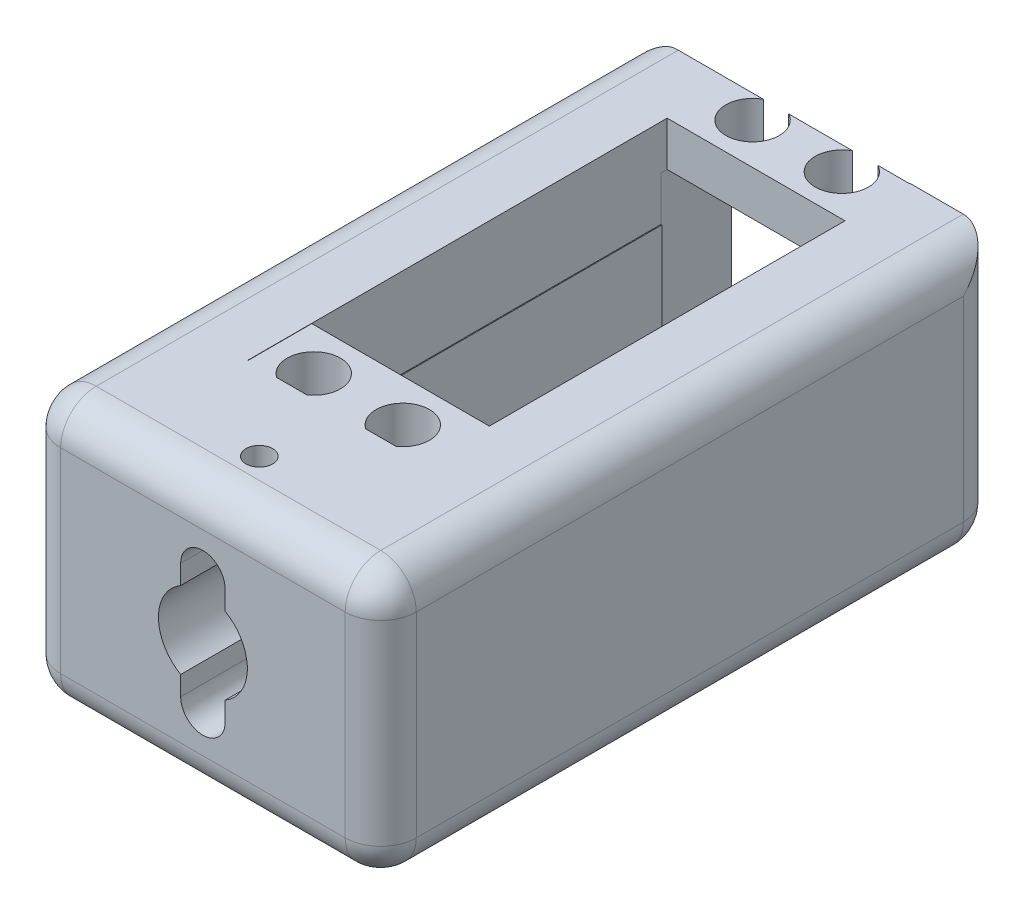
SolidWorks part; units mm, degrees
ref_plane "Front Plane" through (0, 0, 0) normal (0, 0, 1) x (1, 0, 0)
ref_plane "Top Plane" through (0, 0, 0) normal (0, 1, 0) x (1, 0, 0)
ref_plane "Right Plane" through (0, 0, 0) normal (1, 0, 0) x (0, 0, -1)
sketch "Sketch3" plane through (0, 27.7, 0) normal (0, -1, 0) x (1, 0, 0)
  line L0 (10, 7.15) -> (10, -0.3675) construction
  line L1 (-9.9707, 7.2207) -> (10, 7.2207)
  line L2 (-9.9707, 7.2207) -> (-9.9707, 0)
  line L3 (-9.9707, 0) -> (10, 0)
  line L4 (10, 7.2207) -> (10, 0)
  arc A0 (-9.9, 7.25) -> (-10, 7.15) centre (-9.9, 7.15) ccw construction
extrude "Boss-Extrude2" add sketch "Sketch3" along normal blind 10
sketch "Sketch4" plane through (10, 0, 0) normal (1, 0, 0) x (0, 0, -1)
  line L1 (-7.2207, 27.7) -> (47.3058, 27.7)
  line L2 (-7.2207, 27.7) -> (-7.2207, 17.7)
  line L3 (-7.2207, 17.7) -> (47.3058, 17.7)
  line L4 (47.3058, 27.7) -> (47.3058, 17.7)
extrude "Boss-Extrude3" add sketch "Sketch4" along normal blind 10
sketch "Sketch5" plane through (10, 0, 0) normal (-1, 0, 0) x (0, 0, 1)
  line L0 (-40, 11.1) -> (-40, 27.6) construction
  line L1 (-47.25, 27.8) -> (-40, 27.8)
  line L2 (-47.25, 27.8) -> (-47.25, 17.7)
  line L3 (-47.25, 17.7) -> (-40, 17.7)
  line L4 (-40, 27.8) -> (-40, 17.7)
  line L5 (0, 17.7) -> (-47.3058, 17.7) construction
extrude "Boss-Extrude4" add sketch "Sketch5" along normal blind 20
sketch "Sketch6" plane through (-10, 0, 0) normal (-1, 0, 0) x (0, 0, 1)
  line L1 (-47.25, 17.7) -> (7.2207, 17.7)
  line L2 (-47.25, 17.7) -> (-47.25, 27.7)
  line L3 (-47.25, 27.7) -> (7.2207, 27.7)
  line L4 (7.2207, 17.7) -> (7.2207, 27.7)
extrude "Boss-Extrude5" add sketch "Sketch6" along normal blind 10
sketch "Sketch7" plane through (0, 27.8, 0) normal (0, 1, 0) x (1, 0, 0)
  circle A0 centre (-5.0006, 44.6092) radius 3
  circle A1 centre (5.0371, 44.6092) radius 2.9988
extrude "Cut-Extrude1" cut sketch "Sketch7" against normal blind 12
sketch "Sketch8" plane through (0, 27.7, 0) normal (0, 1, 0) x (1, 0, 0)
  circle A0 centre (-5, -4.75) radius 3
  circle A1 centre (5.0146, -4.75) radius 3
extrude "Cut-Extrude2" cut sketch "Sketch8" against normal blind 12
sketch "Sketch9" plane through (0, 17.7, 0) normal (0, -1, 0) x (1, 0, 0)
  line L1 (-20, 7.2207) -> (20, 7.2207)
  line L2 (-20, 7.2207) -> (-20, -47.3058)
  line L3 (-20, -47.3058) -> (20, -47.3058)
  line L4 (20, 7.2207) -> (20, -47.3058)
  line L5 (-9.9, 0) -> (10, 0)
  line L6 (-9.9, 0) -> (-9.9, -40)
  line L7 (-9.9, -40) -> (10, -40)
  line L8 (10, 0) -> (10, -40)
extrude "Boss-Extrude8" add sketch "Sketch9" along normal blind 12
sketch "Sketch10" plane through (0, 0, -47.3058) normal (0, 0, -1) x (-1, 0, 0)
  line L0 (-20, 27.7) -> (-10, 27.7) construction
  line L1 (-10, 27.7) -> (10.06, 27.7)
  line L2 (-10, 27.7) -> (-10, 5.7)
  line L3 (-10, 5.7) -> (10.06, 5.7)
  line L4 (10.06, 27.7) -> (10.06, 5.7)
  line L5 (20, 5.7) -> (-20, 5.7) construction
  line L7 (-10, 27.7) -> (10.06, 27.7)
  line L8 (-10, 27.7) -> (-10, 22.7)
  line L9 (-10, 22.7) -> (10.06, 22.7)
  line L10 (10.06, 27.7) -> (10.06, 22.7)
  line M3 (-10, 17.7) -> (-10, 27.7)
  line M6 (-20, 5.7) -> (20, 5.7)
  line M8 (20, 17.7) -> (-10, 17.7)
  dimension "D1" = 5
extrude "Cut-Extrude6" cut sketch "Sketch10" against normal blind 8 contours L4 L2 M8 M6 | L9 L4 M3 M8 region at (-0.03, 20.2, -47.3058) region at (-0.03, 11.7, -47.3058)
sketch "Sketch11" plane through (0, 0, 7.2207) normal (0, 0, 1) x (1, 0, 0)
  line L1 (-20, 27.7) -> (20, 27.7)
  line L2 (-20, 27.7) -> (-20, 5.7)
  line L3 (-20, 5.7) -> (20, 5.7)
  line L4 (20, 27.7) -> (20, 5.7)
extrude "Boss-Extrude9" add sketch "Sketch11" along normal blind 5
sketch "Sketch12" plane through (10, 0, 0) normal (1, 0, 0) x (0, 0, -1)
  line L1 (40, 27.8) -> (47.25, 27.8)
  line L2 (40, 27.8) -> (40, 27.7)
  line L3 (40, 27.7) -> (47.25, 27.7)
  line L4 (47.25, 27.8) -> (47.25, 27.7)
extrude "Cut-Extrude7" cut sketch "Sketch12" against normal blind 20
sketch "Sketch13" plane through (0, 0, 12.2207) normal (0, 0, 1) x (1, 0, 0)
  line L1 (-10, 27.7) -> (10, 27.7)
  line L2 (-10, 27.7) -> (-10, 5.7)
  line L3 (-10, 5.7) -> (10, 5.7)
  line L4 (10, 27.7) -> (10, 5.7)
  line L5 (-10, 22.7) -> (10, 22.7)
  line M2 (-20, 5.7) -> (20, 5.7)
extrude "Cut-Extrude8" cut sketch "Sketch13" against normal blind 20 contours L5 L2 L4 M2 region at (0, 14.2, 12.2207)
sketch "Sketch16" plane through (0, 5.7, 0) normal (0, -1, 0) x (1, 0, 0)
  line L1 (-20, 12.2207) -> (20, 12.2207)
  line L2 (-20, 12.2207) -> (-20, -47.3058)
  line L3 (-20, -47.3058) -> (20, -47.3058)
  line L4 (20, 12.2207) -> (20, -47.3058)
extrude "Boss-Extrude11" add sketch "Sketch16" along normal blind 8
sketch "Sketch17" plane through (0, 5.7, 0) normal (0, 1, 0) x (1, 0, 0)
  line L0 (10, 0.3675) -> (10, -7.15) construction
  line L1 (-10, 40) -> (10, 40)
  line L2 (-10, 40) -> (-10, 0)
  line L3 (-10, 0) -> (10, 0)
  line L4 (10, 40) -> (10, 0)
  line L5 (10, 0) -> (10, -12.2207) construction
extrude "Cut-Extrude10" cut sketch "Sketch17" against normal blind 5
sketch "Sketch19" plane through (0, 0, 12.2207) normal (0, 0, 1) x (1, 0, 0)
  line L0 (20, -2.3) -> (20, 27.7) construction
  line L1 (-20, 27.7) -> (20, 27.7)
  line L2 (-20, 27.7) -> (-20, -2.3)
  line L3 (-20, -2.3) -> (20, -2.3)
  line L4 (20, 27.7) -> (20, -2.3)
extrude "Boss-Extrude12" add sketch "Sketch19" along normal blind 10
sketch "Sketch20" plane through (0, 0, 22.2207) normal (0, 0, 1) x (1, 0, 0)
  line L0 (0, 6.2) -> (0, 19.2) construction
  line L1 (-2.5, 6.2) -> (-2.5, 8.3699)
  line L2 (2.5, 6.2) -> (2.5, 8.3699)
  line L3 (-20, -2.3) -> (20, -2.3) construction
  line L4 (-2.5, 17.0301) -> (-2.5, 19.2)
  line L5 (2.5, 17.0301) -> (2.5, 19.2)
  arc A0 (-2.5, 6.2) -> (2.5, 6.2) centre (0, 6.2) ccw
  arc A1 (2.5, 19.2) -> (-2.5, 19.2) centre (0, 19.2) ccw
  arc A2 (-2.5, 17.0301) -> (-2.5, 8.3699) centre (0, 12.7) ccw
  arc A3 (2.5, 8.3699) -> (2.5, 17.0301) centre (0, 12.7) ccw
  point P3 (0, 12.7)
  dimension "D3" = 2.5
  dimension "D1" = 13
  dimension "D2" = 15
extrude "Cut-Extrude11" cut sketch "Sketch20" against normal blind 8
sketch "Sketch21" plane through (0, 27.7, 0) normal (0, 1, 0) x (1, 0, 0)
  line L0 (-20, -22.2207) -> (-20, 47.25) construction
  circle A0 centre (0, -15.8709) radius 1.5
  dimension "D1" = 20
extrude "Cut-Extrude12" cut sketch "Sketch21" against normal blind 30
fillet "Fillet2" radius 4 11 edges at (20, 27.7, -12.5425) (-20, 27.7, -12.5146) (-20, -2.3, -12.5425) (20, -2.3, -12.5425) (0, -2.3, -47.3058) (0, -2.3, 22.2207) (0, 27.7, 22.2207) (-20, 7.7, -47.3058) (20, 12.7, -47.3058) (20, 12.7, 22.2207) (-20, 12.7, 22.2207)
sketch "Sketch22" plane through (-20, 0, 0) normal (-1, 0, 0) x (0, 0, 1)
  line L0 (18.2207, 23.7) -> (-43.3058, 23.7) construction
  line L1 (-40.5342, 23.7) -> (9.637, 23.7)
  line L2 (-40.5342, 23.7) -> (-40.5342, 1.7)
  line L3 (-40.5342, 1.7) -> (9.637, 1.7)
  line L4 (9.637, 23.7) -> (9.637, 1.7)
  line L5 (-43.3058, 1.7) -> (18.2207, 1.7) construction
